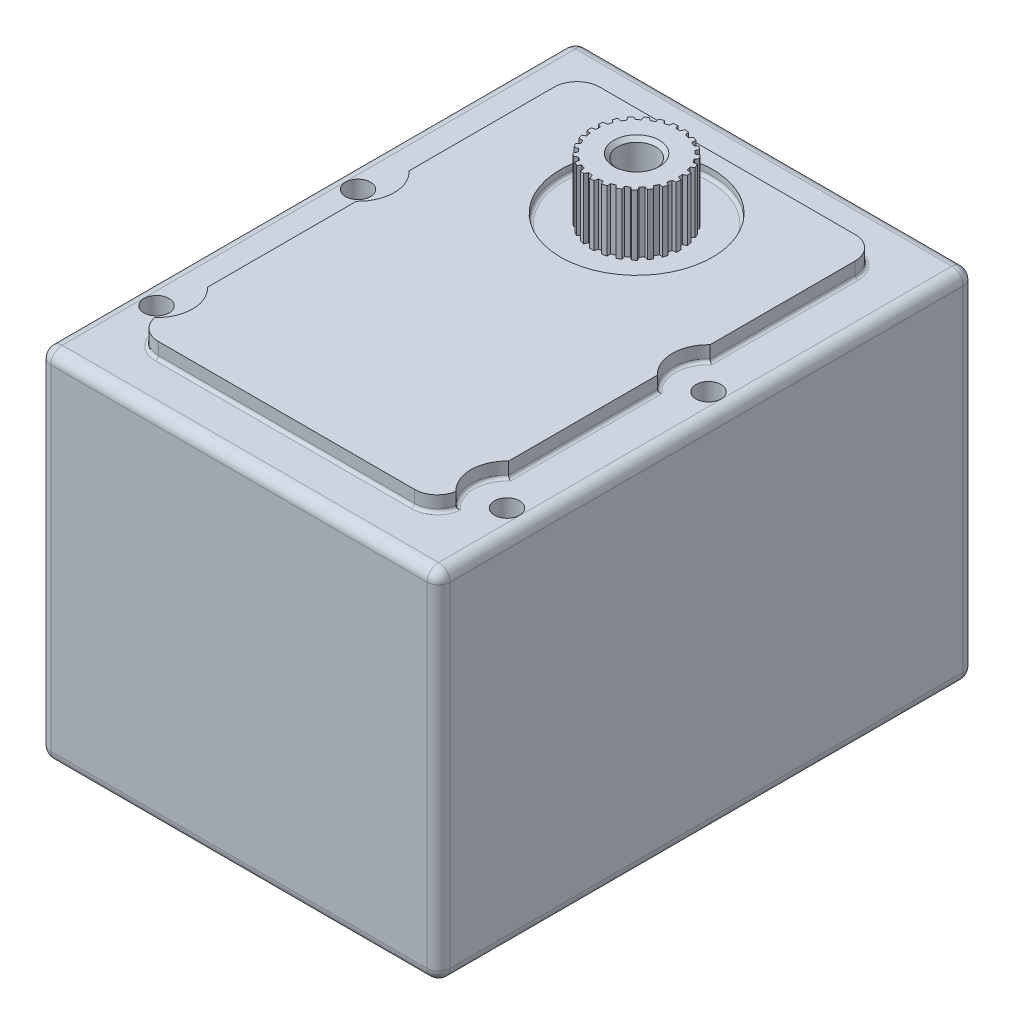
SolidWorks part; units mm, degrees
ref_plane "Front Plane" through (0, 0, 0) normal (0, 0, 1) x (1, 0, 0)
ref_plane "Top Plane" through (0, 0, 0) normal (0, 1, 0) x (1, 0, 0)
ref_plane "Right Plane" through (0, 0, 0) normal (1, 0, 0) x (0, 0, -1)
sketch "Sketch1" plane through (0, 0, 0) normal (0, 1, 0) x (1, 0, 0)
  line L0 (-169.0576, 189.3802) -> (-169.0576, 212.3802) construction
  line L1 (13.125, -17.625) -> (-13.125, -17.625)
  line L2 (13.125, -17.625) -> (13.125, 17.625)
  line L3 (13.125, 17.625) -> (-13.125, 17.625)
  line L4 (-13.125, -17.625) -> (-13.125, 17.625)
  line L5 (13.125, -17.625) -> (-13.125, 17.625) construction
  line L6 (13.125, 17.625) -> (-13.125, -17.625) construction
  line L7 (-10.428, -17.5178) -> (-10.428, 17.4822) construction
  line L9 (9.9, -14.5) -> (-9.9, -14.5) construction
  line L10 (9.9, -14.5) -> (9.9, 14.5) construction
  line L11 (9.9, 14.5) -> (-9.9, 14.5) construction
  line L12 (-9.9, -14.5) -> (-9.9, 14.5) construction
  line L13 (9.9, -14.5) -> (-9.9, 14.5) construction
  line L14 (9.9, 14.5) -> (-9.9, -14.5) construction
  line L15 (-11.525, 1.725) -> (11.525, 1.725) construction
  line L16 (-11.525, 1.725) -> (-11.525, -11.525) construction
  line L17 (-11.525, -11.525) -> (11.525, -11.525) construction
  line L18 (11.525, 1.725) -> (11.525, -11.525) construction
  circle A0 centre (0, 8.525) radius 5 construction
  circle A1 centre (-11.525, 1.725) radius 2.375 construction
  point P0 (0, 0)
  point P10 (0, 0)
  point P19 (0, -11.525)
  dimension "D10" = 10
  dimension "D12" = 4.75
  dimension "D1" = 26.25
  dimension "D2" = 35.25
  dimension "D3" = 23
  dimension "D4" = 35
  dimension "D5" = 29
  dimension "D6" = 19.8
  dimension "D7" = 23.05
  dimension "D8" = 13.25
  dimension "D9" = 6.1
  dimension "D11" = 9.1
extrude "Boss-Extrude1" add sketch "Sketch1" along normal blind 24.5
sketch "Sketch2" plane through (0, 24.5, 0) normal (0, 1, 0) x (1, 0, 0)
  circle A0 centre (0, 8.525) radius 2.95
  circle A1 centre (0, 8.525) radius 5 construction
  dimension "D1" = 5.9
extrude "Boss-Extrude2" add sketch "Sketch2" along normal blind 3.41
sketch "Sketch4" plane through (0, 24.5, 0) normal (0, 1, 0) x (1, 0, 0)
  line L0 (9.9, -14.5) -> (9.9, 14.5) construction
  line L1 (9.9, -14.5) -> (-9.9, -14.5) construction
  line L2 (-9.9, -14.5) -> (-9.9, 14.5) construction
  line L3 (9.9, 14.5) -> (-9.9, 14.5) construction
  line L4 (9.9, -14.5) -> (9.9, -13.2571)
  line L5 (9.9, -14.5) -> (-9.9, -14.5)
  line L6 (-9.9, -14.5) -> (-9.9, -13.2571)
  line L7 (9.9, 14.5) -> (-9.9, 14.5)
  line L8 (-9.9, 3.4571) -> (-9.9, 14.5)
  line L9 (9.9, 3.4571) -> (9.9, 14.5)
  line L10 (9.9, -9.7929) -> (9.9, -0.0071)
  line L11 (-9.9, -9.7929) -> (-9.9, -0.0071)
  arc A0 (9.9, 3.4571) -> (9.9, -0.0071) centre (11.525, 1.725) ccw
  arc A1 (9.9, -9.7929) -> (9.9, -13.2571) centre (11.525, -11.525) ccw
  arc A2 (-9.9, -13.2571) -> (-9.9, -9.7929) centre (-11.525, -11.525) ccw
  circle A3 centre (-11.525, 1.725) radius 2.375 construction
  arc A4 (-9.9, -0.0071) -> (-9.9, 3.4571) centre (-11.525, 1.725) ccw
extrude "Cut-Extrude1" cut sketch "Sketch4" against normal blind 1 flip side to cut
sketch "Sketch6" plane through (0, 24.5, 0) normal (0, 1, 0) x (1, 0, 0)
  circle A0 centre (0, 8.525) radius 5 construction
  circle A1 centre (0, 8.525) radius 5
  circle A2 centre (0, 8.525) radius 2.95 construction
  circle A3 centre (0, 8.525) radius 2.95
extrude "Cut-Extrude3" cut sketch "Sketch6" against normal blind 0.59
sketch "Sketch5" plane through (0, 27.91, 0) normal (0, 1, 0) x (1, 0, 0)
  line L0 (-0.2265, 11.4663) -> (-0.1437, 11.2388)
  line L1 (-0.1437, 11.2388) -> (0.1437, 11.2388)
  line L2 (0.1437, 11.2388) -> (0.2265, 11.4663)
  line L3 (0, 8.525) -> (0, 11.475) construction
  line L4 (0.5121, 11.4302) -> (0.5357, 11.1893)
  line L5 (0.5357, 11.1893) -> (0.8141, 11.1178)
  line L6 (0.8141, 11.1178) -> (0.9509, 11.3175)
  line L7 (0, 8.525) -> (0.7336, 11.3823) construction
  line L8 (1.2185, 11.2116) -> (1.1814, 10.9723)
  line L9 (1.1814, 10.9723) -> (1.4333, 10.8339)
  line L10 (1.4333, 10.8339) -> (1.6155, 10.9933)
  line L11 (0, 8.525) -> (1.4212, 11.1101) construction
  line L12 (1.8483, 10.8242) -> (1.7529, 10.6016)
  line L13 (1.7529, 10.6016) -> (1.9625, 10.4049)
  line L14 (1.9625, 10.4049) -> (2.1786, 10.514)
  line L15 (0, 8.525) -> (2.0194, 10.6755) construction
  line L16 (2.362, 10.2923) -> (2.2143, 10.1005)
  line L17 (2.2143, 10.1005) -> (2.3683, 9.8578)
  line L18 (2.3683, 9.8578) -> (2.6048, 9.9098)
  line L19 (0, 8.525) -> (2.4908, 10.1057) construction
  line L20 (2.7273, 9.6493) -> (2.5365, 9.5003)
  line L21 (2.5365, 9.5003) -> (2.6254, 9.2269)
  line L22 (2.6254, 9.2269) -> (2.8673, 9.2185)
  line L23 (0, 8.525) -> (2.8056, 9.4366) construction
  line L24 (2.9213, 8.9358) -> (2.6994, 8.8388)
  line L25 (2.6994, 8.8388) -> (2.7175, 8.552)
  line L26 (2.7175, 8.552) -> (2.9497, 8.4836)
  line L27 (0, 8.525) -> (2.9442, 8.7102) construction
  line L28 (2.9316, 8.1964) -> (2.6926, 8.1577)
  line L29 (2.6926, 8.1577) -> (2.6388, 7.8753)
  line L30 (2.6388, 7.8753) -> (2.8467, 7.7513)
  line L31 (0, 8.525) -> (2.8977, 7.9722) construction
  line L32 (2.7578, 7.4776) -> (2.5167, 7.4996)
  line L33 (2.5167, 7.4996) -> (2.3943, 7.2395)
  line L34 (2.3943, 7.2395) -> (2.5649, 7.0677)
  line L35 (0, 8.525) -> (2.6692, 7.269) construction
  line L36 (2.4107, 6.8247) -> (2.1826, 6.9059)
  line L37 (2.1826, 6.9059) -> (1.9994, 6.6844)
  line L38 (1.9994, 6.6844) -> (2.1219, 6.4756)
  line L39 (0, 8.525) -> (2.273, 6.6446) construction
  line L40 (1.9121, 6.2786) -> (1.7114, 6.414)
  line L41 (1.7114, 6.414) -> (1.4788, 6.245)
  line L42 (1.4788, 6.245) -> (1.5456, 6.0123)
  line L43 (0, 8.525) -> (1.734, 6.1384) construction
  line L44 (1.2934, 5.8736) -> (1.1326, 6.0547)
  line L45 (1.1326, 6.0547) -> (0.8654, 5.9489)
  line L46 (0.8654, 5.9489) -> (0.8721, 5.7069)
  line L47 (0, 8.525) -> (1.086, 5.7822) construction
  line L48 (0.5934, 5.6353) -> (0.4827, 5.8506)
  line L49 (0.4827, 5.8506) -> (0.1975, 5.8146)
  line L50 (0.1975, 5.8146) -> (0.1439, 5.5785)
  line L51 (0, 8.525) -> (0.3697, 5.5983) construction
  line L52 (-0.1439, 5.5785) -> (-0.1975, 5.8146)
  line L53 (-0.1975, 5.8146) -> (-0.4827, 5.8506)
  line L54 (-0.4827, 5.8506) -> (-0.5934, 5.6353)
  line L55 (0, 8.525) -> (-0.3697, 5.5983) construction
  line L56 (-0.8721, 5.7069) -> (-0.8654, 5.9489)
  line L57 (-0.8654, 5.9489) -> (-1.1326, 6.0547)
  line L58 (-1.1326, 6.0547) -> (-1.2934, 5.8736)
  line L59 (0, 8.525) -> (-1.086, 5.7822) construction
  line L60 (-1.5456, 6.0123) -> (-1.4788, 6.245)
  line L61 (-1.4788, 6.245) -> (-1.7114, 6.414)
  line L62 (-1.7114, 6.414) -> (-1.9121, 6.2786)
  line L63 (0, 8.525) -> (-1.734, 6.1384) construction
  line L64 (-2.1219, 6.4756) -> (-1.9994, 6.6844)
  line L65 (-1.9994, 6.6844) -> (-2.1826, 6.9059)
  line L66 (-2.1826, 6.9059) -> (-2.4107, 6.8247)
  line L67 (0, 8.525) -> (-2.273, 6.6446) construction
  line L68 (-2.5649, 7.0677) -> (-2.3943, 7.2395)
  line L69 (-2.3943, 7.2395) -> (-2.5167, 7.4996)
  line L70 (-2.5167, 7.4996) -> (-2.7578, 7.4776)
  line L71 (0, 8.525) -> (-2.6692, 7.269) construction
  line L72 (-2.8467, 7.7513) -> (-2.6388, 7.8753)
  line L73 (-2.6388, 7.8753) -> (-2.6926, 8.1577)
  line L74 (-2.6926, 8.1577) -> (-2.9316, 8.1964)
  line L75 (0, 8.525) -> (-2.8977, 7.9722) construction
  line L76 (-2.9497, 8.4836) -> (-2.7175, 8.552)
  line L77 (-2.7175, 8.552) -> (-2.6994, 8.8388)
  line L78 (-2.6994, 8.8388) -> (-2.9213, 8.9358)
  line L79 (0, 8.525) -> (-2.9442, 8.7102) construction
  line L80 (-2.8673, 9.2185) -> (-2.6254, 9.2269)
  line L81 (-2.6254, 9.2269) -> (-2.5365, 9.5003)
  line L82 (-2.5365, 9.5003) -> (-2.7273, 9.6493)
  line L83 (0, 8.525) -> (-2.8056, 9.4366) construction
  line L84 (-2.6048, 9.9098) -> (-2.3683, 9.8578)
  line L85 (-2.3683, 9.8578) -> (-2.2143, 10.1005)
  line L86 (-2.2143, 10.1005) -> (-2.362, 10.2923)
  line L87 (0, 8.525) -> (-2.4908, 10.1057) construction
  line L88 (-2.1786, 10.514) -> (-1.9625, 10.4049)
  line L89 (-1.9625, 10.4049) -> (-1.7529, 10.6016)
  line L90 (-1.7529, 10.6016) -> (-1.8483, 10.8242)
  line L91 (0, 8.525) -> (-2.0194, 10.6755) construction
  line L92 (-1.6155, 10.9933) -> (-1.4333, 10.8339)
  line L93 (-1.4333, 10.8339) -> (-1.1814, 10.9723)
  line L94 (-1.1814, 10.9723) -> (-1.2185, 11.2116)
  line L95 (0, 8.525) -> (-1.4212, 11.1101) construction
  line L96 (-0.9509, 11.3175) -> (-0.8141, 11.1178)
  line L97 (-0.8141, 11.1178) -> (-0.5357, 11.1893)
  line L98 (-0.5357, 11.1893) -> (-0.5121, 11.4302)
  line L99 (0, 8.525) -> (-0.7336, 11.3823) construction
  arc A0 (0.2265, 11.4663) -> (-0.2265, 11.4663) centre (0, 8.525) ccw
  circle A1 centre (0, 8.525) radius 2.95 construction
  arc A2 (0.9509, 11.3175) -> (0.5121, 11.4302) centre (0, 8.525) ccw
  arc A3 (1.6155, 10.9933) -> (1.2185, 11.2116) centre (0, 8.525) ccw
  arc A4 (2.1786, 10.514) -> (1.8483, 10.8242) centre (0, 8.525) ccw
  arc A5 (2.6048, 9.9098) -> (2.362, 10.2923) centre (0, 8.525) ccw
  arc A6 (2.8673, 9.2185) -> (2.7273, 9.6493) centre (0, 8.525) ccw
  arc A7 (2.9497, 8.4836) -> (2.9213, 8.9358) centre (0, 8.525) ccw
  arc A8 (2.8467, 7.7513) -> (2.9316, 8.1964) centre (0, 8.525) ccw
  arc A9 (2.5649, 7.0677) -> (2.7578, 7.4776) centre (0, 8.525) ccw
  arc A10 (2.1219, 6.4756) -> (2.4107, 6.8247) centre (0, 8.525) ccw
  arc A11 (1.5456, 6.0123) -> (1.9121, 6.2786) centre (0, 8.525) ccw
  arc A12 (0.8721, 5.7069) -> (1.2934, 5.8736) centre (0, 8.525) ccw
  arc A13 (0.1439, 5.5785) -> (0.5934, 5.6353) centre (0, 8.525) ccw
  arc A14 (-0.5934, 5.6353) -> (-0.1439, 5.5785) centre (0, 8.525) ccw
  arc A15 (-1.2934, 5.8736) -> (-0.8721, 5.7069) centre (0, 8.525) ccw
  arc A16 (-1.9121, 6.2786) -> (-1.5456, 6.0123) centre (0, 8.525) ccw
  arc A17 (-2.4107, 6.8247) -> (-2.1219, 6.4756) centre (0, 8.525) ccw
  arc A18 (-2.7578, 7.4776) -> (-2.5649, 7.0677) centre (0, 8.525) ccw
  arc A19 (-2.9316, 8.1964) -> (-2.8467, 7.7513) centre (0, 8.525) ccw
  arc A20 (-2.9213, 8.9358) -> (-2.9497, 8.4836) centre (0, 8.525) ccw
  arc A21 (-2.7273, 9.6493) -> (-2.8673, 9.2185) centre (0, 8.525) ccw
  arc A22 (-2.362, 10.2923) -> (-2.6048, 9.9098) centre (0, 8.525) ccw
  arc A23 (-1.8483, 10.8242) -> (-2.1786, 10.514) centre (0, 8.525) ccw
  arc A24 (-1.2185, 11.2116) -> (-1.6155, 10.9933) centre (0, 8.525) ccw
  arc A25 (-0.5121, 11.4302) -> (-0.9509, 11.3175) centre (0, 8.525) ccw
  point P3 (0, 11.2388)
  point P14 (0, 8.525)
  point P133 (0, 8.525)
  dimension "D1" = 110
  dimension "D2" = 0.2362
  dimension "D3" = 0.2874
  dimension "D4" = 25
extrude "Cut-Extrude4" cut sketch "Sketch5" against normal up to surface (4 mm away) up to face at (0, 23.91, -5.575)
sketch "Sketch7" plane through (0, 23.5, 0) normal (0, 1, 0) x (1, 0, 0)
  circle A0 centre (-11.525, 1.725) radius 0.825
  circle A1 centre (11.525, 1.725) radius 0.825
  circle A2 centre (11.525, -11.525) radius 0.825
  circle A3 centre (-11.525, -11.525) radius 0.825
  dimension "D1" = 1.65
extrude "Cut-Extrude5" cut sketch "Sketch7" against normal blind 4
fillet "Fillet1" radius 1.5 4 edges at (9.9, 24, -14.5) (-9.9, 24, -14.5) (9.9, 24, 14.5) (-9.9, 24, 14.5)
fillet "Fillet2" radius 0.75 12 edges at (0, 0, 17.625) (13.125, 0, 0) (-13.125, 0, 0) (0, 0, -17.625) (-13.125, 11.75, -17.625) (13.125, 11.75, -17.625) (13.125, 11.75, 17.625) (-13.125, 11.75, 17.625) (0, 23.5, 17.625) (13.125, 23.5, 0) (0, 23.5, -17.625) (-13.125, 23.5, 0)
fillet "Fillet3" radius 0.2 15 edges at (-9.9, 23.5, -8.2285) (-9.4607, 23.5, -14.0607) (0, 23.5, -14.5) (9.4607, 23.5, -14.0607) (-9.3877, 23.5, 14.1479) (9.3877, 23.5, 14.1479) (-9.15, 23.5, -1.725) (0, 23.91, -3.525) (9.9, 23.5, -8.2285) (9.15, 23.5, -1.725) (9.9, 23.5, 4.9) (9.15, 23.5, 11.525) (-9.9, 23.5, 4.9) (-9.15, 23.5, 11.525) (0, 23.5, 14.5)
sketch "Sketch8" plane through (0, 27.91, 0) normal (0, 1, 0) x (1, 0, 0)
  circle A0 centre (0, 8.525) radius 1.25
  dimension "D1" = 2.5
extrude "Cut-Extrude7" cut sketch "Sketch8" against normal blind 5
chamfer "Chamfer1" distance 0.25 angle 45 1 edges at (0, 27.91, -7.275)
extrude "Cut-Extrude8" cut sketch "Sketch7<2>" along normal blind 4 from surface starting at face at (0, 0, 0)
sketch "Sketch7<2>" plane through (0, 23.5, 0) normal (0, 1, 0) x (1, 0, 0) same geometry as "Sketch7"
sketch "Sketch10" plane through (0, 0, 0) normal (0, -1, 0) x (1, 0, 0)
  line L0 (-12.375, 17.625) -> (12.375, 17.625) construction
  line L1 (-10, 14.825) -> (10, 14.825)
  line L2 (-10, 14.825) -> (-10, 4.475)
  line L3 (-10, 4.475) -> (10, 4.475)
  line L4 (10, 14.825) -> (10, 4.475)
  line L5 (-10, -0.825) -> (10, -0.825)
  line L6 (-10, -0.825) -> (-10, -14.825)
  line L7 (-10, -14.825) -> (10, -14.825)
  line L8 (10, -0.825) -> (10, -14.825)
  line L9 (12.375, -17.625) -> (-12.375, -17.625) construction
  point P8 (0, 14.825)
  dimension "D1" = 20
  dimension "D2" = 2.8
  dimension "D3" = 14
  dimension "D4" = 2.8
  dimension "D5" = 5.3
extrude "Boss-Extrude3" add sketch "Sketch10" along normal blind 2.5 draft 20
sketch "Sketch11" plane through (0, -2.5, 0) normal (0, -1, 0) x (-1, 0, 0)
  circle A0 centre (0, 8.525) radius 2.8
  circle A1 centre (0, 8.525) radius 2.125
  dimension "D1" = 5.6
  dimension "D2" = 4.25
extrude "Boss-Extrude4" add sketch "Sketch11" along normal blind 0.3
sketch "Sketch12" plane through (0, -2.5, 0) normal (0, -1, 0) x (1, 0, 0)
  circle A0 centre (0, -8.525) radius 2.125 construction
  circle A1 centre (0, -8.525) radius 2.125
extrude "Cut-Extrude9" cut sketch "Sketch12" against normal blind 5
